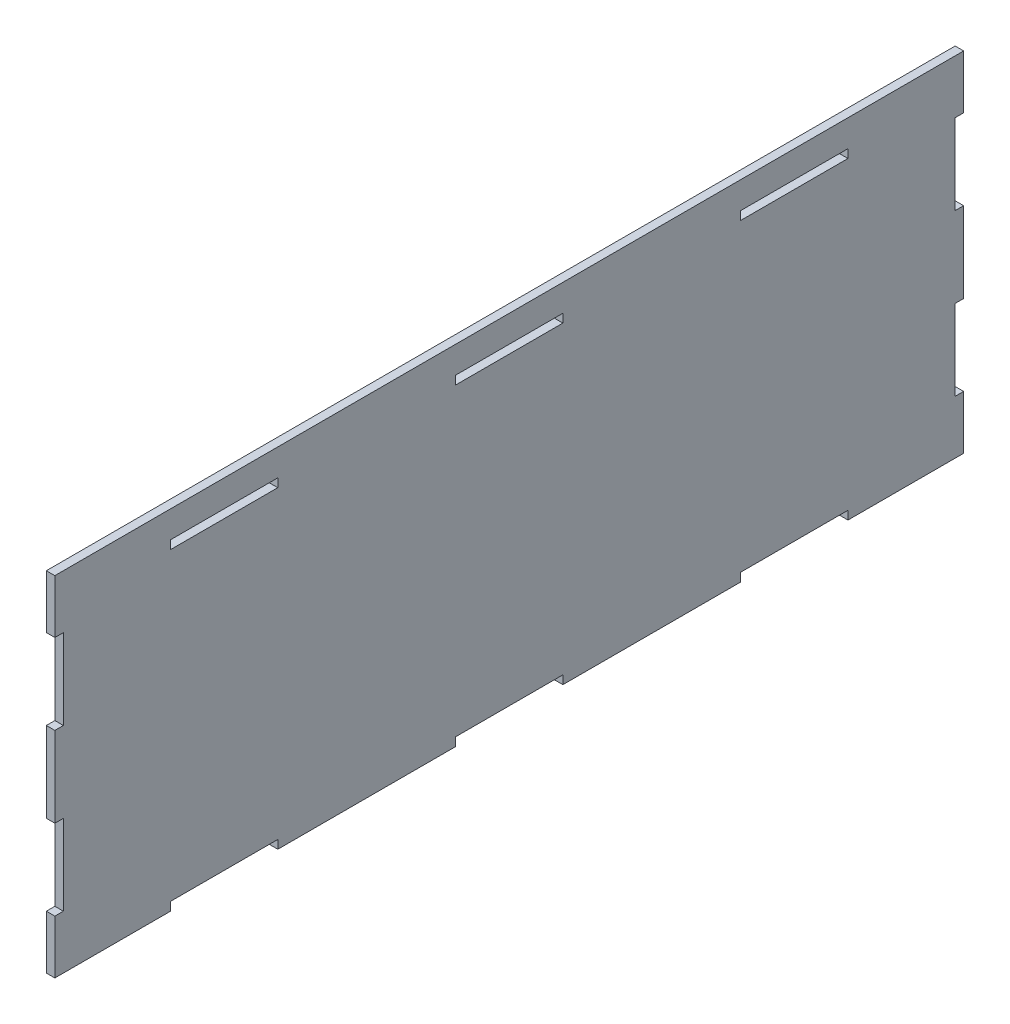
SolidWorks part; units mm, degrees
ref_plane "前视" through (0, 0, 0) normal (0, 0, 1) x (1, 0, 0)
ref_plane "上视" through (0, 0, 0) normal (0, 1, 0) x (1, 0, 0)
ref_plane "右视" through (0, 0, 0) normal (1, 0, 0) x (0, 0, -1)
sketch "Sketch1" plane through (0, 0, 0) normal (1, 0, 0) x (0, 0, -1)
  line L1 (0, 0) -> (339.05, 0)
  line L2 (0, 0) -> (0, -130)
  line L3 (0, -130) -> (339.05, -130)
  line L4 (339.05, 0) -> (339.05, -130)
  dimension "D1" = 339.05
  dimension "D2" = 130
extrude "Boss-Extrude1" add sketch "Sketch1" along normal blind 3.175
ref_axis "Axis1" through (3.175, 0, -169.525) along (0, 1, 0)
sketch "Sketch2" plane through (3.175, 0, 0) normal (1, 0, 0) x (0, 0, -1)
  line L0 (0, -130) -> (339.05, -130) construction
  line L1 (43.175, -10) -> (83.175, -10)
  line L2 (43.175, -10) -> (43.175, -13.175)
  line L3 (43.175, -13.175) -> (83.175, -13.175)
  line L4 (83.175, -10) -> (83.175, -13.175)
  line L5 (0, 0) -> (0, -130) construction
  line L6 (339.05, -130) -> (339.05, 0) construction
  line L7 (149.525, -10) -> (189.525, -10)
  line L8 (149.525, -10) -> (149.525, -13.175)
  line L9 (149.525, -13.175) -> (189.525, -13.175)
  line L10 (189.525, -10) -> (189.525, -13.175)
  line L11 (255.875, -10) -> (295.875, -10)
  line L12 (255.875, -10) -> (255.875, -13.175)
  line L13 (255.875, -13.175) -> (295.875, -13.175)
  line L14 (295.875, -10) -> (295.875, -13.175)
  line L15 (339.05, -20) -> (335.875, -20)
  line L16 (339.05, -20) -> (339.05, -50)
  line L17 (339.05, -50) -> (335.875, -50)
  line L18 (335.875, -20) -> (335.875, -50)
  line L19 (339.05, 0) -> (0, 0) construction
  line L21 (339.05, -80) -> (335.875, -80)
  line L22 (339.05, -80) -> (339.05, -110)
  line L23 (339.05, -110) -> (335.875, -110)
  line L24 (335.875, -80) -> (335.875, -110)
  line L25 (0, -20) -> (3.175, -20)
  line L26 (0, -20) -> (0, -50)
  line L27 (0, -50) -> (3.175, -50)
  line L28 (3.175, -20) -> (3.175, -50)
  line L29 (0, -80) -> (3.175, -80)
  line L30 (0, -80) -> (0, -110)
  line L31 (0, -110) -> (3.175, -110)
  line L32 (3.175, -80) -> (3.175, -110)
  dimension "D1" = 120
  dimension "D2" = 3.175
  dimension "D3" = 43.175
  dimension "D4" = 40
  dimension "D5" = 66.35
  dimension "D6" = 40
  dimension "D7" = 40
  dimension "D8" = 66.35
  dimension "D9" = 20
  dimension "D10" = 3.175
  dimension "D11" = 30
  dimension "D12" = 30
  dimension "D13" = 30
  dimension "D14" = 20
  dimension "D15" = 30
  dimension "D16" = 3.175
  dimension "D17" = 30
  dimension "D18" = 30
  dimension "D19" = 3.175
  dimension "D20" = 10
extrude "Cut-Extrude1" cut sketch "Sketch2" against normal blind 10
sketch "Sketch3" plane through (3.175, 0, 0) normal (1, 0, 0) x (0, 0, -1)
  line L0 (43.18, -130) -> (83.18, -130)
  line L1 (43.18, -130) -> (43.18, -126.825)
  line L2 (83.18, -130) -> (83.18, -126.825)
  line L3 (43.18, -126.825) -> (83.18, -126.825)
  line L4 (0, -130) -> (339.05, -130) construction
  line L10 (0, -110) -> (0, -130) construction
  dimension "D1" = 3.175
  dimension "D2" = 40
  dimension "D3" = 43.18
extrude "Cut-Extrude2" cut sketch "Sketch3" against normal through all
pattern_linear "LPattern1" count 3 spacing 106.35 along (0, 0, -1) of "Cut-Extrude2"
